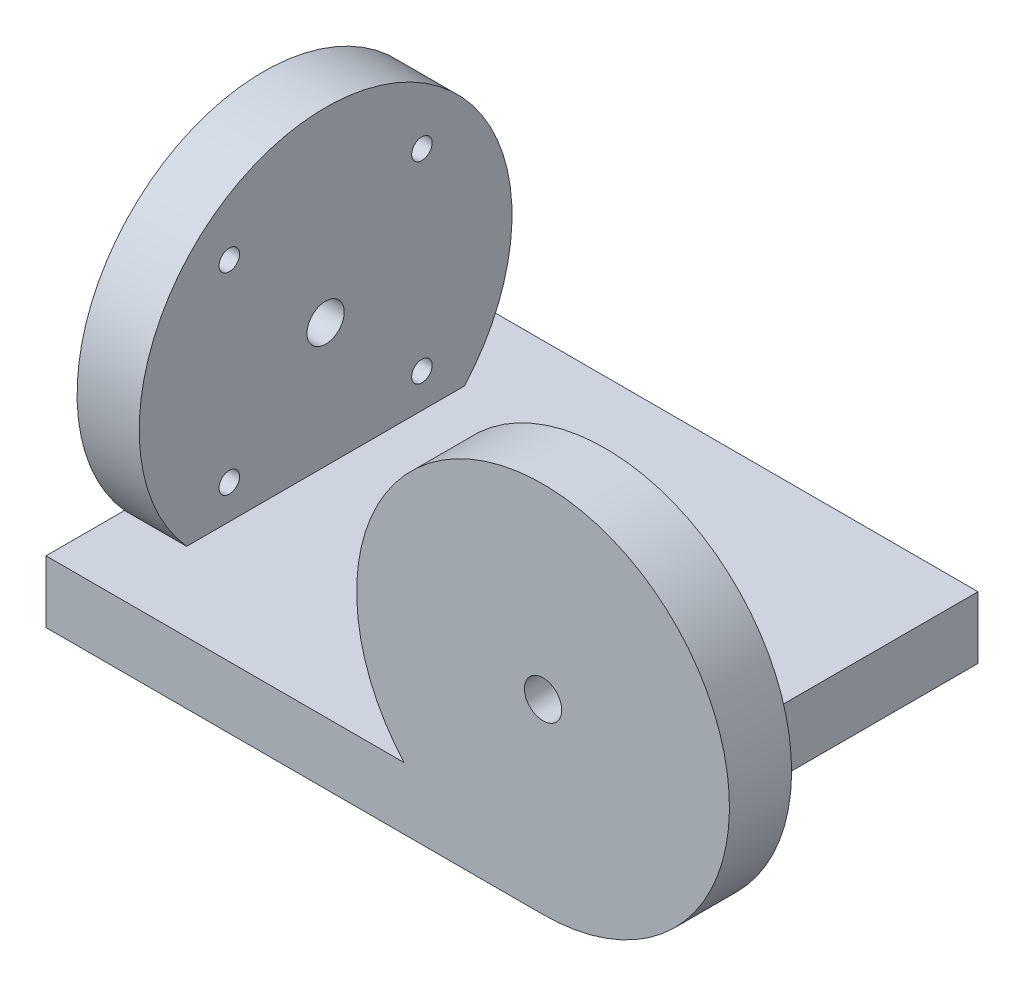
SolidWorks part; units mm, degrees
ref_plane "Front Plane" through (0, 0, 0) normal (0, 0, 1) x (1, 0, 0)
ref_plane "Top Plane" through (0, 0, 0) normal (0, 1, 0) x (1, 0, 0)
ref_plane "Right Plane" through (0, 0, 0) normal (1, 0, 0) x (0, 0, -1)
sketch "Sketch1" plane through (0, 0, 0) normal (0, 0, 1) x (1, 0, 0)
  circle A0 centre (0, 0) radius 30
  dimension "D1" = 60
extrude "Boss-Extrude1" add sketch "Sketch1" along normal blind 10 contours A0
sketch "Sketch2" plane through (0, 0, 10) normal (0, 0, 1) x (1, 0, 0)
  line L1 (0, -30) -> (-80, -30)
  line L2 (0, -30) -> (0, -20)
  line L3 (0, -20) -> (-80, -20)
  line L4 (-80, -30) -> (-80, -20)
  circle A0 centre (0, 0) radius 30 construction
  dimension "D1" = 10
  dimension "D2" = 80
extrude "Boss-Extrude2" add sketch "Sketch2" against normal blind 70
sketch "Sketch3" plane through (-80, 0, 0) normal (-1, 0, 0) x (0, 0, 1)
  line L1 (-60, -20) -> (10, -20) construction
  line L2 (-60, -30) -> (10, -30) construction
  circle A1 centre (-25, 0) radius 30
  point P5 (-25, -20)
  dimension "D1" = 60
extrude "Boss-Extrude3" add sketch "Sketch3" against normal blind 10 contours A1
hole_wizard "Ø6.0mm Dowel Hole2" positions "Sketch6" profile "Sketch7" hole size "Ø6.0" standard "ANSI Metric" end condition through all
sketch "Sketch6" plane through (0, 0, 0) normal (0, 0, -1) x (-1, 0, 0)
  point P0 (0, 0)
sketch "Sketch7" plane through (0, 0, 0) normal (1, 0, 0) x (0, 1, 0)
  line L0 (0, 0) -> (0, 10)
  line L1 (0, 10) -> (3, 10)
  line L2 (3, 10) -> (3, 0)
  line L5 (3, 0) -> (0, 0)
  line L11 (0, -6.35) -> (0, 107.95) construction
  dimension "Thru Hole Dia." = 6
  dimension "Thru Hole Depth" = 10
hole_wizard "M4x0.7 Tapped Hole1" positions "Sketch8" profile "Sketch9" tap size "M4x0.7" standard "ANSI Metric"
sketch "Sketch8" plane through (0, 0, 0) normal (0, 0, -1) x (-1, 0, 0)
  point P0 (-15.5, 15.5)
  point P2 (15.5, 15.5)
  point P4 (15.5, -15.5)
  point P6 (-15.5, -15.5)
  dimension "D1" = 31
  dimension "D2" = 31
  dimension "D3" = 15.5
  dimension "D4" = 15.5
sketch "Sketch9" plane through (15.5, 15.5, 0) normal (1, 0, 0) x (0, 1, 0)
  line L0 (0, 0) -> (0, 6.9914)
  line L1 (0, 6.9914) -> (1.65, 6)
  line L2 (1.65, 6) -> (1.65, 0)
  line L5 (1.65, 0) -> (0, 0)
  line L10 (0, 6.9914) -> (-1.65, 6) construction
  line L11 (0, -6.35) -> (0, 107.95) construction
  dimension "Tap Drill Dia." = 3.3
  dimension "Tap Drill Depth" = 6
  dimension "Drill Angle" = 118
cosmetic thread "Hole Thread1" parameters "D1"=5, "D2"=4
cosmetic thread "Hole Thread2" parameters "D1"=5, "D2"=4
cosmetic thread "Hole Thread3" parameters "D1"=5, "D2"=4
cosmetic thread "Hole Thread4" parameters "D1"=5, "D2"=4
hole_wizard "Ø6.0mm Dowel Hole3" positions "Sketch11" profile "Sketch13" hole size "Ø6.0" standard "ANSI Metric" end condition through all
sketch "Sketch11" plane through (-70, 1.0061, -20.9934) normal (1, 0, 0) x (0, 0, -1)
  point P0 (4.0066, -1.0061)
  point P4 (4.0066, -1.0061)
  point P7 (0, 0)
  point P8 (4.0066, -1.0061)
sketch "Sketch13" plane through (-70, 0, -25) normal (0, 1, 0) x (0, 0, -1)
  line L0 (0, 0) -> (0, 10)
  line L1 (0, 10) -> (3, 10)
  line L2 (3, 10) -> (3, 0)
  line L5 (3, 0) -> (0, 0)
  line L11 (0, -6.35) -> (0, 107.95) construction
  dimension "Thru Hole Dia." = 6
  dimension "Thru Hole Depth" = 10
hole_wizard "M4x0.7 Tapped Hole2" positions "Sketch15" profile "Sketch17" tap size "M4x0.7" standard "ANSI Metric"
sketch "Sketch15" plane through (-70, 1.0061, -20.9934) normal (1, 0, 0) x (0, 0, -1)
  circle A14 centre (4.0066, -1.0061) radius 3 construction
  point P0 (-11.4934, 15.5)
  point P2 (19.5066, 15.5)
  point P4 (19.5066, -15.5)
  point P6 (-11.4934, -15.5)
  point P19 (0, 0)
  point P20 (0, 0)
  dimension "D1" = 31
  dimension "D2" = 31
  dimension "D3" = 15.5
sketch "Sketch17" plane through (-70, 16.5061, -9.5) normal (0, 1, 0) x (0, 0, -1)
  line L0 (0, 0) -> (0, 6.9914)
  line L1 (0, 6.9914) -> (1.65, 6)
  line L2 (1.65, 6) -> (1.65, 0)
  line L5 (1.65, 0) -> (0, 0)
  line L10 (0, 6.9914) -> (-1.65, 6) construction
  line L11 (0, -6.35) -> (0, 107.95) construction
  dimension "Tap Drill Dia." = 3.3
  dimension "Tap Drill Depth" = 6
  dimension "Drill Angle" = 118
cosmetic thread "Hole Thread5" parameters "D1"=5, "D2"=4
cosmetic thread "Hole Thread6" parameters "D1"=5, "D2"=4
cosmetic thread "Hole Thread7" parameters "D1"=5, "D2"=4
cosmetic thread "Hole Thread8" parameters "D1"=5, "D2"=4
